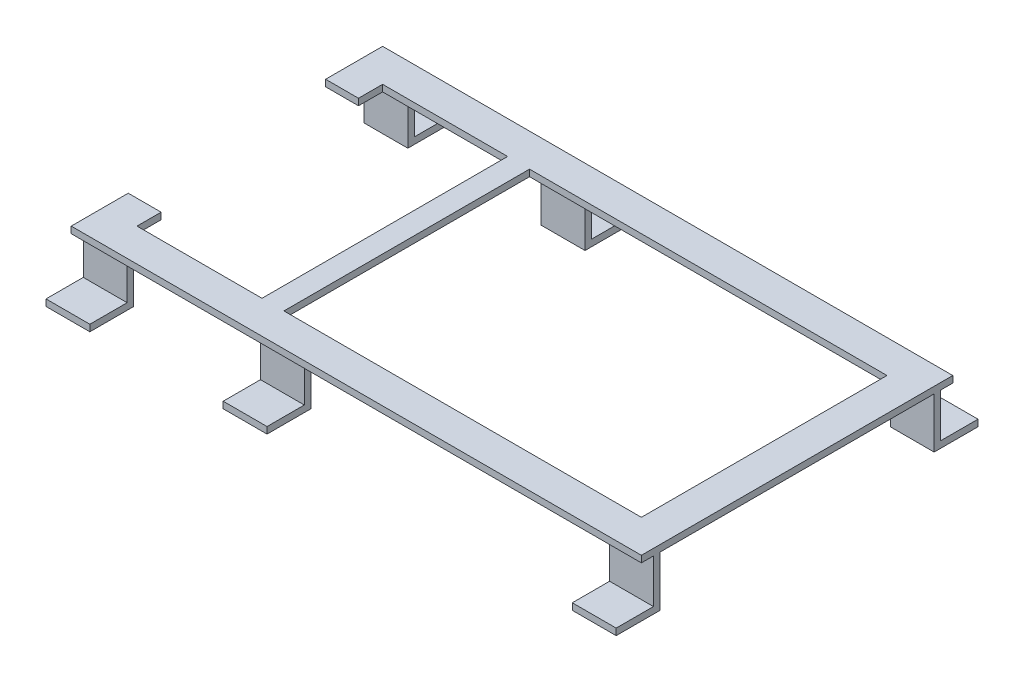
SolidWorks part; units mm, degrees
ref_plane "Alzado" through (0, 0, 0) normal (0, 0, 1) x (1, 0, 0)
ref_plane "Planta" through (0, 0, 0) normal (0, 1, 0) x (1, 0, 0)
ref_plane "Vista lateral" through (0, 0, 0) normal (1, 0, 0) x (0, 0, -1)
sketch "Croquis1" plane through (0, 0, 0) normal (0, 1, 0) x (1, 0, 0)
  line L0 (115, 56) -> (-115, 56)
  line L1 (130, -71) -> (-130, -71)
  line L2 (130, -71) -> (130, 71)
  line L3 (130, 71) -> (-130, 71)
  line L4 (-130, -71) -> (-130, 71)
  line L5 (130, -71) -> (-130, 71) construction
  line L6 (130, 71) -> (-130, -71) construction
  line L7 (-115, -56) -> (-115, 56)
  line L8 (115, -56) -> (-115, -56)
  line L9 (115, -56) -> (115, 56)
  point P0 (0, 0)
  dimension "D1" = 142
  dimension "D2" = 260
  dimension "D3" = 15
extrude "Saliente-Extruir1" add sketch "Croquis1" along normal blind 3
ref_plane "Plano1" through (-130, 0, 0) normal (1, 0, 0) x (0, 0, -1)
sketch "Croquis2" plane through (-130, 0, 0) normal (-1, 0, 0) x (0, 0, 1)
  line L0 (65.5, 0) -> (65.5, -20)
  line L6 (62.5, 0) -> (65.5, 0)
  line L8 (82.5, -23) -> (82.5, -20)
  line L9 (82.5, -20) -> (65.5, -20)
  line L20 (62.5, 0) -> (62.5, -23)
  line L21 (62.5, -23) -> (82.5, -23)
  line L22 (71, 3) -> (71, 0) construction
  line L23 (-71, 0) -> (71, 0) construction
  dimension "D1" = 23
  dimension "D2" = 3
  dimension "D3" = 5.5
  dimension "D4" = 20
  dimension "D5" = 3
extrude "Saliente-Extruir2" add sketch "Croquis2" against normal blind 20
mirror "Simetría1" about plane through (0, 0, 0) normal (1, 0, 0) of "Saliente-Extruir2"
mirror "Simetría2" about plane through (0, 0, 0) normal (0, 0, 1) of "Simetría1"
sketch "Croquis3" plane through (0, 3, 0) normal (0, 1, 0) x (1, 0, 0)
  line L1 (-120, 32.5) -> (-60, 32.5)
  line L2 (-120, 32.5) -> (-120, -32.5)
  line L3 (-120, -32.5) -> (-60, -32.5)
  line L4 (-60, 32.5) -> (-60, -32.5)
  point P4 (-60, 0)
  dimension "D1" = 65
  dimension "D2" = 60
  dimension "D3" = 60
extrude "Cortar-Extruir1" [suppressed] cut sketch "Croquis3" against normal through all
mirror "Simetría3" [suppressed] about plane through (0, 0, 0) normal (1, 0, 0)
ref_plane "Plano2" through (-39.2, 0, 0) normal (1, 0, 0) x (0, 0, -1)
sketch "Croquis4" plane through (-39.2, 0, 0) normal (1, 0, 0) x (0, 0, -1)
  line L12 (-71, 0) -> (-65.5, 0)
  line L13 (-65.5, 0) -> (-65.5, -20)
  line L14 (-65.5, -20) -> (-82.5, -20)
  line L15 (-82.5, -20) -> (-82.5, -23)
  line L16 (-82.5, -23) -> (-62.5, -23)
  line L17 (-82.5, -23) -> (-62.5, -23)
  line L19 (-65.5, 0) -> (-65.5, -20)
  line L20 (-65.5, -20) -> (-82.5, -20)
  line L21 (-82.5, -20) -> (-82.5, -23)
  line L38 (-62.5, -23) -> (-62.5, 0)
  line L40 (-62.5, -23) -> (-62.5, 0)
  line L42 (62.5, 0) -> (62.5, -23)
  line L44 (62.5, 0) -> (62.5, -23)
  line L47 (62.5, -23) -> (82.5, -23)
  line L49 (82.5, -23) -> (82.5, -20)
  line L50 (62.5, -23) -> (82.5, -23)
  line L54 (82.5, -23) -> (82.5, -20)
  line L56 (82.5, -20) -> (65.5, -20)
  line L58 (82.5, -20) -> (65.5, -20)
  line L60 (71, 0) -> (71, 3)
  line L61 (71, 0) -> (71, 3)
  line L62 (71, 3) -> (-71, 3)
  line L63 (71, 3) -> (-71, 3)
  line L70 (-71, 0) -> (-65.5, 0)
  line L71 (-62.5, 0) -> (62.5, 0)
  line L72 (-62.5, 0) -> (62.5, 0)
  line L73 (65.5, -20) -> (65.5, 0)
  line L74 (65.5, -20) -> (65.5, 0)
  line L75 (65.5, 0) -> (71, 0)
  line L76 (65.5, 0) -> (71, 0)
  line L77 (-71, 3) -> (-71, 0)
  line L78 (-71, 3) -> (-71, 0)
  dimension "D1" = 0
extrude "Saliente-Extruir3" add sketch "Croquis4" along normal mid plane 20
mirror "Simetría4" about plane through (0, 0, 0) normal (0, 0, 1) of "Saliente-Extruir3"
sketch "Croquis5" plane through (0, 3, 0) normal (0, 1, 0) x (1, 0, 0)
  line L1 (-105.499, -45) -> (-143.7054, -45)
  line L2 (-105.499, -45) -> (-105.499, 45)
  line L3 (-105.499, 45) -> (-143.7054, 45)
  line L4 (-143.7054, -45) -> (-143.7054, 45)
  line L5 (-105.499, -45) -> (-143.7054, 45) construction
  line L6 (-105.499, 45) -> (-143.7054, -45) construction
  point P0 (-124.6022, 0)
  dimension "D1" = 90
extrude "Cortar-Extruir2" cut sketch "Croquis5" against normal through all
sketch "Croquis7" plane through (0, 3, 0) normal (0, 1, 0) x (1, 0, 0)
  line L0 (-49.2, 56) -> (-49.2, -56) construction
  line L1 (-49.2, 56) -> (-29.2, 56)
  line L2 (-49.2, 56) -> (-49.2, -56)
  line L3 (-49.2, -56) -> (-29.2, -56)
  line L4 (-29.2, 56) -> (-29.2, -56)
extrude "Cortar-Extruir3" cut sketch "Croquis7" against normal through all
sketch "Croquis6" plane through (0, 3, 0) normal (0, 1, 0) x (1, 0, 0)
  line L0 (-53, 56) -> (-53, -56) construction
  line L1 (115, 56) -> (-115, 56) construction
  line L2 (-115, -56) -> (115, -56) construction
  line L4 (-130, -45) -> (-130, -71) construction
  line L6 (-58, 56) -> (-48, 56)
  line L7 (-58, 56) -> (-58, -56)
  line L8 (-58, -56) -> (-48, -56)
  line L9 (-48, 56) -> (-48, -56)
  point P12 (-53, 56)
  point P13 (-53, -56)
  dimension "D1" = 77
  dimension "D2" = 10
extrude "Saliente-Extruir4" add sketch "Croquis6" against normal up to surface (3 mm away) up to face at (-39.2, 0, -64)
